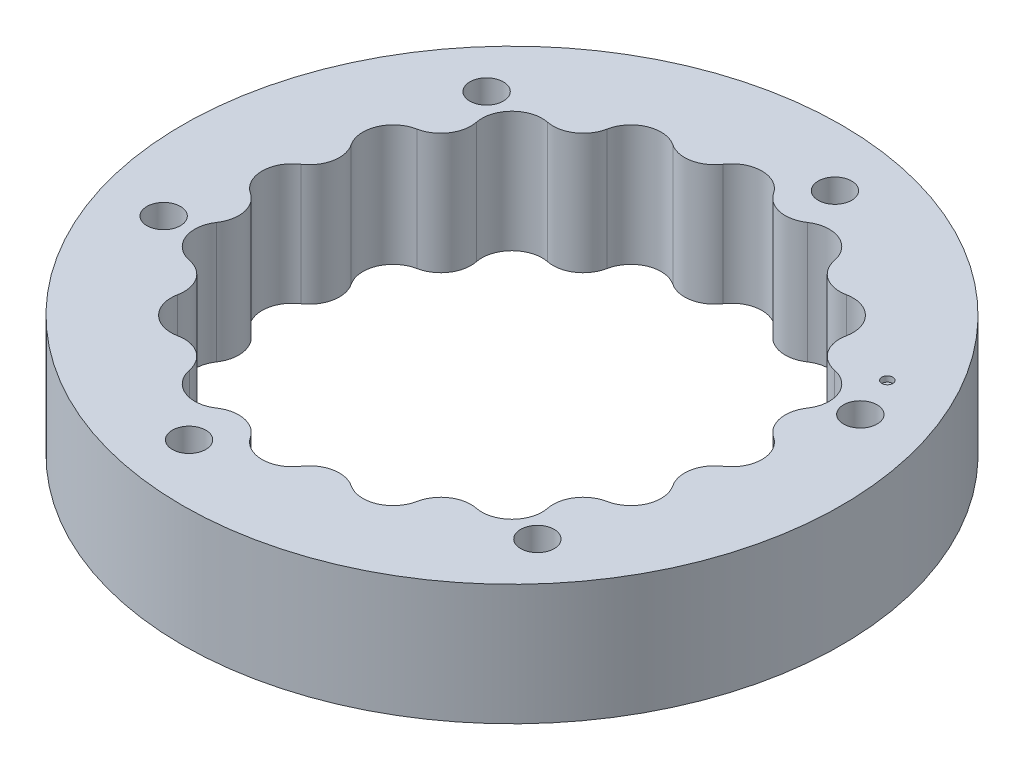
SolidWorks part; units mm, degrees
ref_plane "Front Plane" through (0, 0, 0) normal (0, 0, 1) x (1, 0, 0)
ref_plane "Top Plane" through (0, 0, 0) normal (0, 1, 0) x (1, 0, 0)
ref_plane "Right Plane" through (0, 0, 0) normal (1, 0, 0) x (0, 0, -1)
sketch "Sketch1" plane through (0, 0, 0) normal (0, 1, 0) x (1, 0, 0)
  arc A0 (-31.5919, 24.5347) -> (-34.7568, 19.7981) centre (0, 0) ccw
  arc A1 (4.9902, 39.6875) -> (-4.9902, 39.6875) centre (0, 40) ccw
  arc A2 (19.7981, 34.7568) -> (10.5774, 38.5761) centre (15.3073, 36.9552) ccw
  arc A3 (-31.5919, 24.5347) -> (-34.7568, 19.7981) centre (0, 0) ccw construction
  arc A4 (31.5919, 24.5347) -> (24.5347, 31.5919) centre (28.2843, 28.2843) ccw
  arc A5 (-31.5919, 24.5347) -> (-34.7568, 19.7981) centre (0, 0) ccw construction
  arc A6 (38.5761, 10.5774) -> (34.7568, 19.7981) centre (36.9552, 15.3073) ccw
  arc A7 (-31.5919, 24.5347) -> (-34.7568, 19.7981) centre (0, 0) ccw construction
  arc A8 (39.6875, -4.9902) -> (39.6875, 4.9902) centre (40, 0) ccw
  arc A9 (-31.5919, 24.5347) -> (-34.7568, 19.7981) centre (0, 0) ccw construction
  arc A10 (34.7568, -19.7981) -> (38.5761, -10.5774) centre (36.9552, -15.3073) ccw
  arc A11 (-31.5919, 24.5347) -> (-34.7568, 19.7981) centre (0, 0) ccw construction
  arc A12 (24.5347, -31.5919) -> (31.5919, -24.5347) centre (28.2843, -28.2843) ccw
  arc A13 (-31.5919, 24.5347) -> (-34.7568, 19.7981) centre (0, 0) ccw construction
  arc A14 (10.5774, -38.5761) -> (19.7981, -34.7568) centre (15.3073, -36.9552) ccw
  arc A15 (-31.5919, 24.5347) -> (-34.7568, 19.7981) centre (0, 0) ccw construction
  arc A16 (-4.9902, -39.6875) -> (4.9902, -39.6875) centre (0, -40) ccw
  arc A17 (-31.5919, 24.5347) -> (-34.7568, 19.7981) centre (0, 0) ccw construction
  arc A18 (-19.7981, -34.7568) -> (-10.5774, -38.5761) centre (-15.3073, -36.9552) ccw
  arc A19 (-31.5919, 24.5347) -> (-34.7568, 19.7981) centre (0, 0) ccw construction
  arc A20 (-31.5919, -24.5347) -> (-24.5347, -31.5919) centre (-28.2843, -28.2843) ccw
  arc A21 (-31.5919, 24.5347) -> (-34.7568, 19.7981) centre (0, 0) ccw construction
  arc A22 (-38.5761, -10.5774) -> (-34.7568, -19.7981) centre (-36.9552, -15.3073) ccw
  arc A23 (-31.5919, 24.5347) -> (-34.7568, 19.7981) centre (0, 0) ccw construction
  arc A24 (-39.6875, 4.9902) -> (-39.6875, -4.9902) centre (-40, 0) ccw
  arc A25 (-31.5919, 24.5347) -> (-34.7568, 19.7981) centre (0, 0) ccw construction
  arc A26 (-34.7568, 19.7981) -> (-38.5761, 10.5774) centre (-36.9552, 15.3073) ccw
  arc A27 (-31.5919, 24.5347) -> (-34.7568, 19.7981) centre (0, 0) ccw construction
  arc A28 (-24.5347, 31.5919) -> (-31.5919, 24.5347) centre (-28.2843, 28.2843) ccw
  arc A29 (-31.5919, 24.5347) -> (-34.7568, 19.7981) centre (0, 0) ccw construction
  arc A30 (-10.5774, 38.5761) -> (-19.7981, 34.7568) centre (-15.3073, 36.9552) ccw
  arc A31 (-31.5919, 24.5347) -> (-34.7568, 19.7981) centre (0, 0) ccw construction
  circle A32 centre (0, 0) radius 60
  arc A33 (-19.7981, 34.7568) -> (-24.5347, 31.5919) centre (0, 0) ccw
  arc A34 (-19.7981, 34.7568) -> (-24.5347, 31.5919) centre (0, 0) ccw construction
  arc A35 (-19.7981, 34.7568) -> (-24.5347, 31.5919) centre (0, 0) ccw construction
  arc A36 (-19.7981, 34.7568) -> (-24.5347, 31.5919) centre (0, 0) ccw construction
  arc A37 (-19.7981, 34.7568) -> (-24.5347, 31.5919) centre (0, 0) ccw construction
  arc A38 (-19.7981, 34.7568) -> (-24.5347, 31.5919) centre (0, 0) ccw construction
  arc A39 (-19.7981, 34.7568) -> (-24.5347, 31.5919) centre (0, 0) ccw construction
  arc A40 (-19.7981, 34.7568) -> (-24.5347, 31.5919) centre (0, 0) ccw construction
  arc A41 (-19.7981, 34.7568) -> (-24.5347, 31.5919) centre (0, 0) ccw construction
  arc A42 (-19.7981, 34.7568) -> (-24.5347, 31.5919) centre (0, 0) ccw construction
  arc A43 (-19.7981, 34.7568) -> (-24.5347, 31.5919) centre (0, 0) ccw construction
  arc A44 (-19.7981, 34.7568) -> (-24.5347, 31.5919) centre (0, 0) ccw construction
  arc A45 (-19.7981, 34.7568) -> (-24.5347, 31.5919) centre (0, 0) ccw construction
  arc A46 (-19.7981, 34.7568) -> (-24.5347, 31.5919) centre (0, 0) ccw construction
  arc A47 (-19.7981, 34.7568) -> (-24.5347, 31.5919) centre (0, 0) ccw construction
  arc A48 (-19.7981, 34.7568) -> (-24.5347, 31.5919) centre (0, 0) ccw construction
  arc A49 (-4.9902, 39.6875) -> (-10.5774, 38.5761) centre (0, 0) ccw
  arc A50 (-4.9902, 39.6875) -> (-10.5774, 38.5761) centre (0, 0) ccw construction
  arc A51 (-4.9902, 39.6875) -> (-10.5774, 38.5761) centre (0, 0) ccw construction
  arc A52 (-4.9902, 39.6875) -> (-10.5774, 38.5761) centre (0, 0) ccw construction
  arc A53 (-4.9902, 39.6875) -> (-10.5774, 38.5761) centre (0, 0) ccw construction
  arc A54 (-4.9902, 39.6875) -> (-10.5774, 38.5761) centre (0, 0) ccw construction
  arc A55 (-4.9902, 39.6875) -> (-10.5774, 38.5761) centre (0, 0) ccw construction
  arc A56 (-4.9902, 39.6875) -> (-10.5774, 38.5761) centre (0, 0) ccw construction
  arc A57 (-4.9902, 39.6875) -> (-10.5774, 38.5761) centre (0, 0) ccw construction
  arc A58 (-4.9902, 39.6875) -> (-10.5774, 38.5761) centre (0, 0) ccw construction
  arc A59 (-4.9902, 39.6875) -> (-10.5774, 38.5761) centre (0, 0) ccw construction
  arc A60 (-4.9902, 39.6875) -> (-10.5774, 38.5761) centre (0, 0) ccw construction
  arc A61 (-4.9902, 39.6875) -> (-10.5774, 38.5761) centre (0, 0) ccw construction
  arc A62 (-4.9902, 39.6875) -> (-10.5774, 38.5761) centre (0, 0) ccw construction
  arc A63 (-4.9902, 39.6875) -> (-10.5774, 38.5761) centre (0, 0) ccw construction
  arc A64 (-4.9902, 39.6875) -> (-10.5774, 38.5761) centre (0, 0) ccw construction
  arc A65 (10.5774, 38.5761) -> (4.9902, 39.6875) centre (0, 0) ccw
  arc A66 (10.5774, 38.5761) -> (4.9902, 39.6875) centre (0, 0) ccw construction
  arc A67 (10.5774, 38.5761) -> (4.9902, 39.6875) centre (0, 0) ccw construction
  arc A68 (10.5774, 38.5761) -> (4.9902, 39.6875) centre (0, 0) ccw construction
  arc A69 (10.5774, 38.5761) -> (4.9902, 39.6875) centre (0, 0) ccw construction
  arc A70 (10.5774, 38.5761) -> (4.9902, 39.6875) centre (0, 0) ccw construction
  arc A71 (10.5774, 38.5761) -> (4.9902, 39.6875) centre (0, 0) ccw construction
  arc A72 (10.5774, 38.5761) -> (4.9902, 39.6875) centre (0, 0) ccw construction
  arc A73 (10.5774, 38.5761) -> (4.9902, 39.6875) centre (0, 0) ccw construction
  arc A74 (10.5774, 38.5761) -> (4.9902, 39.6875) centre (0, 0) ccw construction
  arc A75 (10.5774, 38.5761) -> (4.9902, 39.6875) centre (0, 0) ccw construction
  arc A76 (10.5774, 38.5761) -> (4.9902, 39.6875) centre (0, 0) ccw construction
  arc A77 (10.5774, 38.5761) -> (4.9902, 39.6875) centre (0, 0) ccw construction
  arc A78 (10.5774, 38.5761) -> (4.9902, 39.6875) centre (0, 0) ccw construction
  arc A79 (10.5774, 38.5761) -> (4.9902, 39.6875) centre (0, 0) ccw construction
  arc A80 (10.5774, 38.5761) -> (4.9902, 39.6875) centre (0, 0) ccw construction
  arc A81 (24.5347, 31.5919) -> (19.7981, 34.7568) centre (0, 0) ccw
  arc A82 (24.5347, 31.5919) -> (19.7981, 34.7568) centre (0, 0) ccw construction
  arc A83 (24.5347, 31.5919) -> (19.7981, 34.7568) centre (0, 0) ccw construction
  arc A84 (24.5347, 31.5919) -> (19.7981, 34.7568) centre (0, 0) ccw construction
  arc A85 (24.5347, 31.5919) -> (19.7981, 34.7568) centre (0, 0) ccw construction
  arc A86 (24.5347, 31.5919) -> (19.7981, 34.7568) centre (0, 0) ccw construction
  arc A87 (24.5347, 31.5919) -> (19.7981, 34.7568) centre (0, 0) ccw construction
  arc A88 (24.5347, 31.5919) -> (19.7981, 34.7568) centre (0, 0) ccw construction
  arc A89 (24.5347, 31.5919) -> (19.7981, 34.7568) centre (0, 0) ccw construction
  arc A90 (24.5347, 31.5919) -> (19.7981, 34.7568) centre (0, 0) ccw construction
  arc A91 (24.5347, 31.5919) -> (19.7981, 34.7568) centre (0, 0) ccw construction
  arc A92 (24.5347, 31.5919) -> (19.7981, 34.7568) centre (0, 0) ccw construction
  arc A93 (24.5347, 31.5919) -> (19.7981, 34.7568) centre (0, 0) ccw construction
  arc A94 (24.5347, 31.5919) -> (19.7981, 34.7568) centre (0, 0) ccw construction
  arc A95 (24.5347, 31.5919) -> (19.7981, 34.7568) centre (0, 0) ccw construction
  arc A96 (24.5347, 31.5919) -> (19.7981, 34.7568) centre (0, 0) ccw construction
  arc A97 (34.7568, 19.7981) -> (31.5919, 24.5347) centre (0, 0) ccw
  arc A98 (34.7568, 19.7981) -> (31.5919, 24.5347) centre (0, 0) ccw construction
  arc A99 (34.7568, 19.7981) -> (31.5919, 24.5347) centre (0, 0) ccw construction
  arc A100 (34.7568, 19.7981) -> (31.5919, 24.5347) centre (0, 0) ccw construction
  arc A101 (34.7568, 19.7981) -> (31.5919, 24.5347) centre (0, 0) ccw construction
  arc A102 (34.7568, 19.7981) -> (31.5919, 24.5347) centre (0, 0) ccw construction
  arc A103 (34.7568, 19.7981) -> (31.5919, 24.5347) centre (0, 0) ccw construction
  arc A104 (34.7568, 19.7981) -> (31.5919, 24.5347) centre (0, 0) ccw construction
  arc A105 (34.7568, 19.7981) -> (31.5919, 24.5347) centre (0, 0) ccw construction
  arc A106 (34.7568, 19.7981) -> (31.5919, 24.5347) centre (0, 0) ccw construction
  arc A107 (34.7568, 19.7981) -> (31.5919, 24.5347) centre (0, 0) ccw construction
  arc A108 (34.7568, 19.7981) -> (31.5919, 24.5347) centre (0, 0) ccw construction
  arc A109 (34.7568, 19.7981) -> (31.5919, 24.5347) centre (0, 0) ccw construction
  arc A110 (34.7568, 19.7981) -> (31.5919, 24.5347) centre (0, 0) ccw construction
  arc A111 (34.7568, 19.7981) -> (31.5919, 24.5347) centre (0, 0) ccw construction
  arc A112 (34.7568, 19.7981) -> (31.5919, 24.5347) centre (0, 0) ccw construction
  arc A113 (39.6875, 4.9902) -> (38.5761, 10.5774) centre (0, 0) ccw
  arc A114 (39.6875, 4.9902) -> (38.5761, 10.5774) centre (0, 0) ccw construction
  arc A115 (39.6875, 4.9902) -> (38.5761, 10.5774) centre (0, 0) ccw construction
  arc A116 (39.6875, 4.9902) -> (38.5761, 10.5774) centre (0, 0) ccw construction
  arc A117 (39.6875, 4.9902) -> (38.5761, 10.5774) centre (0, 0) ccw construction
  arc A118 (39.6875, 4.9902) -> (38.5761, 10.5774) centre (0, 0) ccw construction
  arc A119 (39.6875, 4.9902) -> (38.5761, 10.5774) centre (0, 0) ccw construction
  arc A120 (39.6875, 4.9902) -> (38.5761, 10.5774) centre (0, 0) ccw construction
  arc A121 (39.6875, 4.9902) -> (38.5761, 10.5774) centre (0, 0) ccw construction
  arc A122 (39.6875, 4.9902) -> (38.5761, 10.5774) centre (0, 0) ccw construction
  arc A123 (39.6875, 4.9902) -> (38.5761, 10.5774) centre (0, 0) ccw construction
  arc A124 (39.6875, 4.9902) -> (38.5761, 10.5774) centre (0, 0) ccw construction
  arc A125 (39.6875, 4.9902) -> (38.5761, 10.5774) centre (0, 0) ccw construction
  arc A126 (39.6875, 4.9902) -> (38.5761, 10.5774) centre (0, 0) ccw construction
  arc A127 (39.6875, 4.9902) -> (38.5761, 10.5774) centre (0, 0) ccw construction
  arc A128 (39.6875, 4.9902) -> (38.5761, 10.5774) centre (0, 0) ccw construction
  arc A129 (38.5761, -10.5774) -> (39.6875, -4.9902) centre (0, 0) ccw
  arc A130 (38.5761, -10.5774) -> (39.6875, -4.9902) centre (0, 0) ccw construction
  arc A131 (38.5761, -10.5774) -> (39.6875, -4.9902) centre (0, 0) ccw construction
  arc A132 (38.5761, -10.5774) -> (39.6875, -4.9902) centre (0, 0) ccw construction
  arc A133 (38.5761, -10.5774) -> (39.6875, -4.9902) centre (0, 0) ccw construction
  arc A134 (38.5761, -10.5774) -> (39.6875, -4.9902) centre (0, 0) ccw construction
  arc A135 (38.5761, -10.5774) -> (39.6875, -4.9902) centre (0, 0) ccw construction
  arc A136 (38.5761, -10.5774) -> (39.6875, -4.9902) centre (0, 0) ccw construction
  arc A137 (38.5761, -10.5774) -> (39.6875, -4.9902) centre (0, 0) ccw construction
  arc A138 (38.5761, -10.5774) -> (39.6875, -4.9902) centre (0, 0) ccw construction
  arc A139 (38.5761, -10.5774) -> (39.6875, -4.9902) centre (0, 0) ccw construction
  arc A140 (38.5761, -10.5774) -> (39.6875, -4.9902) centre (0, 0) ccw construction
  arc A141 (38.5761, -10.5774) -> (39.6875, -4.9902) centre (0, 0) ccw construction
  arc A142 (38.5761, -10.5774) -> (39.6875, -4.9902) centre (0, 0) ccw construction
  arc A143 (38.5761, -10.5774) -> (39.6875, -4.9902) centre (0, 0) ccw construction
  arc A144 (38.5761, -10.5774) -> (39.6875, -4.9902) centre (0, 0) ccw construction
  arc A145 (31.5919, -24.5347) -> (34.7568, -19.7981) centre (0, 0) ccw
  arc A146 (31.5919, -24.5347) -> (34.7568, -19.7981) centre (0, 0) ccw construction
  arc A147 (31.5919, -24.5347) -> (34.7568, -19.7981) centre (0, 0) ccw construction
  arc A148 (31.5919, -24.5347) -> (34.7568, -19.7981) centre (0, 0) ccw construction
  arc A149 (31.5919, -24.5347) -> (34.7568, -19.7981) centre (0, 0) ccw construction
  arc A150 (31.5919, -24.5347) -> (34.7568, -19.7981) centre (0, 0) ccw construction
  arc A151 (31.5919, -24.5347) -> (34.7568, -19.7981) centre (0, 0) ccw construction
  arc A152 (31.5919, -24.5347) -> (34.7568, -19.7981) centre (0, 0) ccw construction
  arc A153 (31.5919, -24.5347) -> (34.7568, -19.7981) centre (0, 0) ccw construction
  arc A154 (31.5919, -24.5347) -> (34.7568, -19.7981) centre (0, 0) ccw construction
  arc A155 (31.5919, -24.5347) -> (34.7568, -19.7981) centre (0, 0) ccw construction
  arc A156 (31.5919, -24.5347) -> (34.7568, -19.7981) centre (0, 0) ccw construction
  arc A157 (31.5919, -24.5347) -> (34.7568, -19.7981) centre (0, 0) ccw construction
  arc A158 (31.5919, -24.5347) -> (34.7568, -19.7981) centre (0, 0) ccw construction
  arc A159 (31.5919, -24.5347) -> (34.7568, -19.7981) centre (0, 0) ccw construction
  arc A160 (31.5919, -24.5347) -> (34.7568, -19.7981) centre (0, 0) ccw construction
  arc A161 (19.7981, -34.7568) -> (24.5347, -31.5919) centre (0, 0) ccw
  arc A162 (19.7981, -34.7568) -> (24.5347, -31.5919) centre (0, 0) ccw construction
  arc A163 (19.7981, -34.7568) -> (24.5347, -31.5919) centre (0, 0) ccw construction
  arc A164 (19.7981, -34.7568) -> (24.5347, -31.5919) centre (0, 0) ccw construction
  arc A165 (19.7981, -34.7568) -> (24.5347, -31.5919) centre (0, 0) ccw construction
  arc A166 (19.7981, -34.7568) -> (24.5347, -31.5919) centre (0, 0) ccw construction
  arc A167 (19.7981, -34.7568) -> (24.5347, -31.5919) centre (0, 0) ccw construction
  arc A168 (19.7981, -34.7568) -> (24.5347, -31.5919) centre (0, 0) ccw construction
  arc A169 (19.7981, -34.7568) -> (24.5347, -31.5919) centre (0, 0) ccw construction
  arc A170 (19.7981, -34.7568) -> (24.5347, -31.5919) centre (0, 0) ccw construction
  arc A171 (19.7981, -34.7568) -> (24.5347, -31.5919) centre (0, 0) ccw construction
  arc A172 (19.7981, -34.7568) -> (24.5347, -31.5919) centre (0, 0) ccw construction
  arc A173 (19.7981, -34.7568) -> (24.5347, -31.5919) centre (0, 0) ccw construction
  arc A174 (19.7981, -34.7568) -> (24.5347, -31.5919) centre (0, 0) ccw construction
  arc A175 (19.7981, -34.7568) -> (24.5347, -31.5919) centre (0, 0) ccw construction
  arc A176 (19.7981, -34.7568) -> (24.5347, -31.5919) centre (0, 0) ccw construction
  arc A177 (4.9902, -39.6875) -> (10.5774, -38.5761) centre (0, 0) ccw
  arc A178 (4.9902, -39.6875) -> (10.5774, -38.5761) centre (0, 0) ccw construction
  arc A179 (4.9902, -39.6875) -> (10.5774, -38.5761) centre (0, 0) ccw construction
  arc A180 (4.9902, -39.6875) -> (10.5774, -38.5761) centre (0, 0) ccw construction
  arc A181 (4.9902, -39.6875) -> (10.5774, -38.5761) centre (0, 0) ccw construction
  arc A182 (4.9902, -39.6875) -> (10.5774, -38.5761) centre (0, 0) ccw construction
  arc A183 (4.9902, -39.6875) -> (10.5774, -38.5761) centre (0, 0) ccw construction
  arc A184 (4.9902, -39.6875) -> (10.5774, -38.5761) centre (0, 0) ccw construction
  arc A185 (4.9902, -39.6875) -> (10.5774, -38.5761) centre (0, 0) ccw construction
  arc A186 (4.9902, -39.6875) -> (10.5774, -38.5761) centre (0, 0) ccw construction
  arc A187 (4.9902, -39.6875) -> (10.5774, -38.5761) centre (0, 0) ccw construction
  arc A188 (4.9902, -39.6875) -> (10.5774, -38.5761) centre (0, 0) ccw construction
  arc A189 (4.9902, -39.6875) -> (10.5774, -38.5761) centre (0, 0) ccw construction
  arc A190 (4.9902, -39.6875) -> (10.5774, -38.5761) centre (0, 0) ccw construction
  arc A191 (4.9902, -39.6875) -> (10.5774, -38.5761) centre (0, 0) ccw construction
  arc A192 (4.9902, -39.6875) -> (10.5774, -38.5761) centre (0, 0) ccw construction
  arc A193 (-10.5774, -38.5761) -> (-4.9902, -39.6875) centre (0, 0) ccw
  arc A194 (-10.5774, -38.5761) -> (-4.9902, -39.6875) centre (0, 0) ccw construction
  arc A195 (-10.5774, -38.5761) -> (-4.9902, -39.6875) centre (0, 0) ccw construction
  arc A196 (-10.5774, -38.5761) -> (-4.9902, -39.6875) centre (0, 0) ccw construction
  arc A197 (-10.5774, -38.5761) -> (-4.9902, -39.6875) centre (0, 0) ccw construction
  arc A198 (-10.5774, -38.5761) -> (-4.9902, -39.6875) centre (0, 0) ccw construction
  arc A199 (-10.5774, -38.5761) -> (-4.9902, -39.6875) centre (0, 0) ccw construction
  arc A200 (-10.5774, -38.5761) -> (-4.9902, -39.6875) centre (0, 0) ccw construction
  arc A201 (-10.5774, -38.5761) -> (-4.9902, -39.6875) centre (0, 0) ccw construction
  arc A202 (-10.5774, -38.5761) -> (-4.9902, -39.6875) centre (0, 0) ccw construction
  arc A203 (-10.5774, -38.5761) -> (-4.9902, -39.6875) centre (0, 0) ccw construction
  arc A204 (-10.5774, -38.5761) -> (-4.9902, -39.6875) centre (0, 0) ccw construction
  arc A205 (-10.5774, -38.5761) -> (-4.9902, -39.6875) centre (0, 0) ccw construction
  arc A206 (-10.5774, -38.5761) -> (-4.9902, -39.6875) centre (0, 0) ccw construction
  arc A207 (-10.5774, -38.5761) -> (-4.9902, -39.6875) centre (0, 0) ccw construction
  arc A208 (-10.5774, -38.5761) -> (-4.9902, -39.6875) centre (0, 0) ccw construction
  arc A209 (-24.5347, -31.5919) -> (-19.7981, -34.7568) centre (0, 0) ccw
  arc A210 (-24.5347, -31.5919) -> (-19.7981, -34.7568) centre (0, 0) ccw construction
  arc A211 (-24.5347, -31.5919) -> (-19.7981, -34.7568) centre (0, 0) ccw construction
  arc A212 (-24.5347, -31.5919) -> (-19.7981, -34.7568) centre (0, 0) ccw construction
  arc A213 (-24.5347, -31.5919) -> (-19.7981, -34.7568) centre (0, 0) ccw construction
  arc A214 (-24.5347, -31.5919) -> (-19.7981, -34.7568) centre (0, 0) ccw construction
  arc A215 (-24.5347, -31.5919) -> (-19.7981, -34.7568) centre (0, 0) ccw construction
  arc A216 (-24.5347, -31.5919) -> (-19.7981, -34.7568) centre (0, 0) ccw construction
  arc A217 (-24.5347, -31.5919) -> (-19.7981, -34.7568) centre (0, 0) ccw construction
  arc A218 (-24.5347, -31.5919) -> (-19.7981, -34.7568) centre (0, 0) ccw construction
  arc A219 (-24.5347, -31.5919) -> (-19.7981, -34.7568) centre (0, 0) ccw construction
  arc A220 (-24.5347, -31.5919) -> (-19.7981, -34.7568) centre (0, 0) ccw construction
  arc A221 (-24.5347, -31.5919) -> (-19.7981, -34.7568) centre (0, 0) ccw construction
  arc A222 (-24.5347, -31.5919) -> (-19.7981, -34.7568) centre (0, 0) ccw construction
  arc A223 (-24.5347, -31.5919) -> (-19.7981, -34.7568) centre (0, 0) ccw construction
  arc A224 (-24.5347, -31.5919) -> (-19.7981, -34.7568) centre (0, 0) ccw construction
  arc A225 (-34.7568, -19.7981) -> (-31.5919, -24.5347) centre (0, 0) ccw
  arc A226 (-34.7568, -19.7981) -> (-31.5919, -24.5347) centre (0, 0) ccw construction
  arc A227 (-34.7568, -19.7981) -> (-31.5919, -24.5347) centre (0, 0) ccw construction
  arc A228 (-34.7568, -19.7981) -> (-31.5919, -24.5347) centre (0, 0) ccw construction
  arc A229 (-34.7568, -19.7981) -> (-31.5919, -24.5347) centre (0, 0) ccw construction
  arc A230 (-34.7568, -19.7981) -> (-31.5919, -24.5347) centre (0, 0) ccw construction
  arc A231 (-34.7568, -19.7981) -> (-31.5919, -24.5347) centre (0, 0) ccw construction
  arc A232 (-34.7568, -19.7981) -> (-31.5919, -24.5347) centre (0, 0) ccw construction
  arc A233 (-34.7568, -19.7981) -> (-31.5919, -24.5347) centre (0, 0) ccw construction
  arc A234 (-34.7568, -19.7981) -> (-31.5919, -24.5347) centre (0, 0) ccw construction
  arc A235 (-34.7568, -19.7981) -> (-31.5919, -24.5347) centre (0, 0) ccw construction
  arc A236 (-34.7568, -19.7981) -> (-31.5919, -24.5347) centre (0, 0) ccw construction
  arc A237 (-34.7568, -19.7981) -> (-31.5919, -24.5347) centre (0, 0) ccw construction
  arc A238 (-34.7568, -19.7981) -> (-31.5919, -24.5347) centre (0, 0) ccw construction
  arc A239 (-34.7568, -19.7981) -> (-31.5919, -24.5347) centre (0, 0) ccw construction
  arc A240 (-34.7568, -19.7981) -> (-31.5919, -24.5347) centre (0, 0) ccw construction
  arc A241 (-39.6875, -4.9902) -> (-38.5761, -10.5774) centre (0, 0) ccw
  arc A242 (-39.6875, -4.9902) -> (-38.5761, -10.5774) centre (0, 0) ccw construction
  arc A243 (-39.6875, -4.9902) -> (-38.5761, -10.5774) centre (0, 0) ccw construction
  arc A244 (-39.6875, -4.9902) -> (-38.5761, -10.5774) centre (0, 0) ccw construction
  arc A245 (-39.6875, -4.9902) -> (-38.5761, -10.5774) centre (0, 0) ccw construction
  arc A246 (-39.6875, -4.9902) -> (-38.5761, -10.5774) centre (0, 0) ccw construction
  arc A247 (-39.6875, -4.9902) -> (-38.5761, -10.5774) centre (0, 0) ccw construction
  arc A248 (-39.6875, -4.9902) -> (-38.5761, -10.5774) centre (0, 0) ccw construction
  arc A249 (-39.6875, -4.9902) -> (-38.5761, -10.5774) centre (0, 0) ccw construction
  arc A250 (-39.6875, -4.9902) -> (-38.5761, -10.5774) centre (0, 0) ccw construction
  arc A251 (-39.6875, -4.9902) -> (-38.5761, -10.5774) centre (0, 0) ccw construction
  arc A252 (-39.6875, -4.9902) -> (-38.5761, -10.5774) centre (0, 0) ccw construction
  arc A253 (-39.6875, -4.9902) -> (-38.5761, -10.5774) centre (0, 0) ccw construction
  arc A254 (-39.6875, -4.9902) -> (-38.5761, -10.5774) centre (0, 0) ccw construction
  arc A255 (-39.6875, -4.9902) -> (-38.5761, -10.5774) centre (0, 0) ccw construction
  arc A256 (-39.6875, -4.9902) -> (-38.5761, -10.5774) centre (0, 0) ccw construction
  arc A257 (-38.5761, 10.5774) -> (-39.6875, 4.9902) centre (0, 0) ccw
  arc A258 (-38.5761, 10.5774) -> (-39.6875, 4.9902) centre (0, 0) ccw construction
  arc A259 (-38.5761, 10.5774) -> (-39.6875, 4.9902) centre (0, 0) ccw construction
  arc A260 (-38.5761, 10.5774) -> (-39.6875, 4.9902) centre (0, 0) ccw construction
  arc A261 (-38.5761, 10.5774) -> (-39.6875, 4.9902) centre (0, 0) ccw construction
  arc A262 (-38.5761, 10.5774) -> (-39.6875, 4.9902) centre (0, 0) ccw construction
  arc A263 (-38.5761, 10.5774) -> (-39.6875, 4.9902) centre (0, 0) ccw construction
  arc A264 (-38.5761, 10.5774) -> (-39.6875, 4.9902) centre (0, 0) ccw construction
  arc A265 (-38.5761, 10.5774) -> (-39.6875, 4.9902) centre (0, 0) ccw construction
  arc A266 (-38.5761, 10.5774) -> (-39.6875, 4.9902) centre (0, 0) ccw construction
  arc A267 (-38.5761, 10.5774) -> (-39.6875, 4.9902) centre (0, 0) ccw construction
  arc A268 (-38.5761, 10.5774) -> (-39.6875, 4.9902) centre (0, 0) ccw construction
  arc A269 (-38.5761, 10.5774) -> (-39.6875, 4.9902) centre (0, 0) ccw construction
  arc A270 (-38.5761, 10.5774) -> (-39.6875, 4.9902) centre (0, 0) ccw construction
  arc A271 (-38.5761, 10.5774) -> (-39.6875, 4.9902) centre (0, 0) ccw construction
  arc A272 (-38.5761, 10.5774) -> (-39.6875, 4.9902) centre (0, 0) ccw construction
  point P52 (0, 0)
  dimension "D1" = 80
  dimension "D2" = 10
  dimension "D4" = 120
  dimension "D3" = 16
extrude "Boss-Extrude1" add sketch "Sketch1" along normal blind 22
fillet "Fillet1" radius 5 32 edges at (-31.5919, 11, -24.5347) (-34.7568, 11, -19.7981) (10.5774, 11, 38.5761) (4.9902, 11, 39.6875) (-4.9902, 11, 39.6875) (-10.5774, 11, 38.5761) (-19.7981, 11, 34.7568) (-24.5347, 11, 31.5919) (-31.5919, 11, 24.5347) (-34.7568, 11, 19.7981) (-38.5761, 11, 10.5774) (-39.6875, 11, 4.9902) (-39.6875, 11, -4.9902) (-38.5761, 11, -10.5774) (19.7981, 11, 34.7568) (24.5347, 11, 31.5919) (31.5919, 11, 24.5347) (34.7568, 11, 19.7981) (38.5761, 11, 10.5774) (39.6875, 11, 4.9902) (39.6875, 11, -4.9902) (38.5761, 11, -10.5774) (34.7568, 11, -19.7981) (31.5919, 11, -24.5347) (24.5347, 11, -31.5919) (19.7981, 11, -34.7568) (10.5774, 11, -38.5761) (4.9902, 11, -39.6875) (-4.9902, 11, -39.6875) (-10.5774, 11, -38.5761) (-19.7981, 11, -34.7568) (-24.5347, 11, -31.5919)
fillet "Fillet2" radius 6 16 edges at (-7.8059, 11, 39.2431) (7.8059, 11, 39.2431) (22.2294, 11, 33.2687) (33.2687, 11, 22.2294) (-22.2294, 11, 33.2687) (-33.2687, 11, 22.2294) (-39.2431, 11, 7.8059) (-39.2431, 11, -7.8059) (39.2431, 11, 7.8059) (39.2431, 11, -7.8059) (33.2687, 11, -22.2294) (22.2294, 11, -33.2687) (7.8059, 11, -39.2431) (-7.8059, 11, -39.2431) (-22.2294, 11, -33.2687) (-33.2687, 11, -22.2294)
sketch "Sketch3" plane through (0, 22, 0) normal (0, 1, 0) x (1, 0, 0)
  line L0 (7.9956, 40.1966) -> (11.7054, 58.8471) construction
  circle A0 centre (0, 0) radius 50 construction
  circle A4 centre (9.7545, 49.0393) radius 3.05
  arc A5 (4.1664, 42.7642) -> (12.5159, 41.1034) centre (9.1661, 46.0813) ccw construction
  circle A6 centre (0, 0) radius 60 construction
  circle A7 centre (47.3465, 16.072) radius 3.05
  circle A8 centre (37.592, -32.9673) radius 3.05
  circle A9 centre (-9.7545, -49.0393) radius 3.05
  circle A10 centre (-47.3465, -16.072) radius 3.05
  circle A11 centre (-37.592, 32.9673) radius 3.05
  point P13 (9.1661, 46.0813)
  point P31 (0, 0)
  dimension "D1" = 100
  dimension "D2" = 6.1
  dimension "D3" = 6
extrude "Cut-Extrude1" cut sketch "Sketch3" against normal through all
ref_axis "Axis1" [suppressed] through (37.592, 0, 32.9673) along (0, 1, 0)
ref_axis "Axis2" [suppressed] through (-9.7545, 0, 49.0393) along (0, 1, 0)
ref_plane "Plane1" [suppressed] through (13.9187, 0, 41.0033) normal (-0.3214, 0, -0.9469) x (-0.9469, 0, 0.3214)
ref_plane "Plane2" [suppressed] through (19.2864, 0, 56.8158) normal (0.3214, 0, 0.9469) x (0.9469, 0, -0.3214)
ref_plane "Plane3" [suppressed] through (19.6078, 0, 57.7627) normal (0.3214, 0, 0.9469) x (0.9469, 0, -0.3214)
ref_plane "Plane4" [suppressed] through (45.1104, 0, 39.5607) normal (0.7518, 0, 0.6593) x (0, -1, 0)
ref_plane "Plane5" [suppressed] through (45.8622, 0, 40.2201) normal (0.7518, 0, 0.6593) x (0, -1, 0)
sketch "Sketch6" [suppressed] plane through (48.3229, 0, 37.4142) normal (-0.7518, 0, -0.6593) x (-0.6593, 0, 0.7518)
  line L0 (-56.2679, 0) -> (63.7321, 0) construction
  line L1 (-22.8416, 17.6775) -> (-2.6943, 26.1971)
  line L2 (10.1584, 26.1971) -> (30.3057, 17.6775)
  line L3 (-22.8416, 4.3225) -> (-2.6943, -4.1971)
  line L4 (10.1584, -4.1971) -> (30.3057, 4.3225)
  arc A0 (-2.6943, -4.1971) -> (10.1584, -4.1971) centre (3.7321, 11) ccw
  arc A1 (30.3057, 4.3225) -> (30.3057, 17.6775) centre (27.4821, 11) ccw
  arc A2 (-22.8416, 17.6775) -> (-22.8416, 4.3225) centre (-20.0179, 11) ccw
  arc A3 (10.1584, 26.1971) -> (-2.6943, 26.1971) centre (3.7321, 11) ccw
  dimension "D1" = 33
  dimension "D2" = 23.75
  dimension "D3" = 23.75
  dimension "D4" = 11
extrude "Boss-Extrude3" [suppressed] add sketch "Sketch6" against normal up to surface (1.3451 mm away)
sketch "Sketch7" [suppressed] plane through (45.8622, 0, 40.2201) normal (0.7518, 0, 0.6593) x (0.6593, 0, -0.7518)
  circle A0 centre (23.75, 11) radius 3.3
  circle A1 centre (-23.75, 11) radius 3.3
  dimension "D1" = 6.6
extrude "Cut-Extrude3" [suppressed] cut sketch "Sketch7" against normal blind 10.5
chamfer "Chamfer2" [suppressed] distance 1 angle 45
fillet "Fillet3" [suppressed] radius 2
sketch "Sketch8" [suppressed] plane through (45.8622, 0, 40.2201) normal (0.7518, 0, 0.6593) x (0.6593, 0, -0.7518)
  line L1 (-16.3518, 22) -> (16.3518, 22)
  line L2 (-16.3518, 22) -> (-16.3518, 27.5)
  line L3 (-16.3518, 27.5) -> (16.3518, 27.5)
  line L4 (16.3518, 22) -> (16.3518, 27.5)
  line L6 (-16.3518, -5.5) -> (16.3518, -5.5)
  line L7 (-16.3518, -5.5) -> (-16.3518, 0)
  line L8 (-16.3518, 0) -> (16.3518, 0)
  line L9 (16.3518, -5.5) -> (16.3518, 0)
  line L10 (26.5737, 4.3225) -> (6.4263, -4.1971) construction
  line L11 (60, 22) -> (-60, 22) construction
  arc A0 (6.4263, 26.1971) -> (-6.4263, 26.1971) centre (0, 11) ccw construction
  arc A1 (-6.4263, -4.1971) -> (6.4263, -4.1971) centre (0, 11) ccw construction
extrude "Cut-Extrude4" [suppressed] cut sketch "Sketch8" against normal through all
sketch "Sketch9" plane through (0, 22, 0) normal (0, 1, 0) x (1, 0, 0)
  circle A0 centre (44.4252, 23.9053) radius 1
  dimension "D1" = 2
extrude "Cut-Extrude5" cut sketch "Sketch9" against normal blind 1
sketch "Sketch10" [suppressed] plane through (0, 22, 0) normal (0, 1, 0) x (1, 0, 0)
  circle A0 centre (44.4252, 23.9053) radius 1
  dimension "D1" = 2
extrude "Cut-Extrude6" [suppressed] cut sketch "Sketch10" against normal blind 1
sketch "Sketch11" plane through (0, 22, 0) normal (0, 1, 0) x (1, 0, 0)
  arc A69 (-43.0406, 4.5831) -> (-43.0406, -4.5831) centre (-40, 0) ccw
  arc A70 (-43.0406, 4.5831) -> (-41.5182, 12.2367) centre (-46.0813, 9.1661) ccw
  arc A71 (-38.0105, 20.7051) -> (-41.5182, 12.2367) centre (-36.9552, 15.3073) ccw
  arc A72 (-38.0105, 20.7051) -> (-33.675, 27.1936) centre (-39.0658, 26.1029) ccw
  arc A73 (-27.1936, 33.675) -> (-33.675, 27.1936) centre (-28.2843, 28.2843) ccw
  arc A74 (-27.1936, 33.675) -> (-20.7051, 38.0105) centre (-26.1029, 39.0658) ccw
  arc A75 (-12.2367, 41.5182) -> (-20.7051, 38.0105) centre (-15.3073, 36.9552) ccw
  arc A76 (-41.5182, -12.2367) -> (-43.0406, -4.5831) centre (-46.0813, -9.1661) ccw
  arc A77 (-41.5182, -12.2367) -> (-38.0105, -20.7051) centre (-36.9552, -15.3073) ccw
  arc A78 (-33.675, -27.1936) -> (-38.0105, -20.7051) centre (-39.0658, -26.1029) ccw
  arc A79 (-33.675, -27.1936) -> (-27.1936, -33.675) centre (-28.2843, -28.2843) ccw
  arc A80 (-20.7051, -38.0105) -> (-27.1936, -33.675) centre (-26.1029, -39.0658) ccw
  arc A81 (-20.7051, -38.0105) -> (-12.2367, -41.5182) centre (-15.3073, -36.9552) ccw
  arc A82 (-4.5831, -43.0406) -> (-12.2367, -41.5182) centre (-9.1661, -46.0813) ccw
  arc A83 (-4.5831, -43.0406) -> (4.5831, -43.0406) centre (0, -40) ccw
  arc A84 (12.2367, -41.5182) -> (4.5831, -43.0406) centre (9.1661, -46.0813) ccw
  arc A85 (12.2367, -41.5182) -> (20.7051, -38.0105) centre (15.3073, -36.9552) ccw
  arc A86 (27.1936, -33.675) -> (20.7051, -38.0105) centre (26.1029, -39.0658) ccw
  arc A87 (27.1936, -33.675) -> (33.675, -27.1936) centre (28.2843, -28.2843) ccw
  arc A88 (38.0105, -20.7051) -> (33.675, -27.1936) centre (39.0658, -26.1029) ccw
  arc A89 (38.0105, -20.7051) -> (41.5182, -12.2367) centre (36.9552, -15.3073) ccw
  arc A90 (43.0406, -4.5831) -> (41.5182, -12.2367) centre (46.0813, -9.1661) ccw
  arc A91 (43.0406, -4.5831) -> (43.0406, 4.5831) centre (40, 0) ccw
  arc A92 (41.5182, 12.2367) -> (43.0406, 4.5831) centre (46.0813, 9.1661) ccw
  arc A93 (41.5182, 12.2367) -> (38.0105, 20.7051) centre (36.9552, 15.3073) ccw
  arc A94 (33.675, 27.1936) -> (38.0105, 20.7051) centre (39.0658, 26.1029) ccw
  arc A95 (33.675, 27.1936) -> (27.1936, 33.675) centre (28.2843, 28.2843) ccw
  arc A96 (20.7051, 38.0105) -> (27.1936, 33.675) centre (26.1029, 39.0658) ccw
  arc A97 (20.7051, 38.0105) -> (12.2367, 41.5182) centre (15.3073, 36.9552) ccw
  arc A98 (4.5831, 43.0406) -> (12.2367, 41.5182) centre (9.1661, 46.0813) ccw
  arc A99 (4.5831, 43.0406) -> (-4.5831, 43.0406) centre (0, 40) ccw
  arc A100 (-12.2367, 41.5182) -> (-4.5831, 43.0406) centre (-9.1661, 46.0813) ccw
  arc A101 (-43.0406, 4.5831) -> (-43.0406, -4.5831) centre (-40, 0) ccw
  arc A102 (-43.0406, 4.5831) -> (-41.5182, 12.2367) centre (-46.0813, 9.1661) ccw
  arc A103 (-38.0105, 20.7051) -> (-41.5182, 12.2367) centre (-36.9552, 15.3073) ccw
  arc A104 (-38.0105, 20.7051) -> (-33.675, 27.1936) centre (-39.0658, 26.1029) ccw
  arc A105 (-27.1936, 33.675) -> (-33.675, 27.1936) centre (-28.2843, 28.2843) ccw
  arc A106 (-27.1936, 33.675) -> (-20.7051, 38.0105) centre (-26.1029, 39.0658) ccw
  arc A107 (-12.2367, 41.5182) -> (-20.7051, 38.0105) centre (-15.3073, 36.9552) ccw
  arc A108 (-41.5182, -12.2367) -> (-43.0406, -4.5831) centre (-46.0813, -9.1661) ccw
  arc A109 (-41.5182, -12.2367) -> (-38.0105, -20.7051) centre (-36.9552, -15.3073) ccw
  arc A110 (-33.675, -27.1936) -> (-38.0105, -20.7051) centre (-39.0658, -26.1029) ccw
  arc A111 (-33.675, -27.1936) -> (-27.1936, -33.675) centre (-28.2843, -28.2843) ccw
  arc A112 (-20.7051, -38.0105) -> (-27.1936, -33.675) centre (-26.1029, -39.0658) ccw
  arc A113 (-20.7051, -38.0105) -> (-12.2367, -41.5182) centre (-15.3073, -36.9552) ccw
  arc A114 (-4.5831, -43.0406) -> (-12.2367, -41.5182) centre (-9.1661, -46.0813) ccw
  arc A115 (-4.5831, -43.0406) -> (4.5831, -43.0406) centre (0, -40) ccw
  arc A116 (12.2367, -41.5182) -> (4.5831, -43.0406) centre (9.1661, -46.0813) ccw
  arc A117 (12.2367, -41.5182) -> (20.7051, -38.0105) centre (15.3073, -36.9552) ccw
  arc A118 (27.1936, -33.675) -> (20.7051, -38.0105) centre (26.1029, -39.0658) ccw
  arc A119 (27.1936, -33.675) -> (33.675, -27.1936) centre (28.2843, -28.2843) ccw
  arc A120 (38.0105, -20.7051) -> (33.675, -27.1936) centre (39.0658, -26.1029) ccw
  arc A121 (38.0105, -20.7051) -> (41.5182, -12.2367) centre (36.9552, -15.3073) ccw
  arc A122 (43.0406, -4.5831) -> (41.5182, -12.2367) centre (46.0813, -9.1661) ccw
  arc A123 (43.0406, -4.5831) -> (43.0406, 4.5831) centre (40, 0) ccw
  arc A124 (41.5182, 12.2367) -> (43.0406, 4.5831) centre (46.0813, 9.1661) ccw
  arc A125 (41.5182, 12.2367) -> (38.0105, 20.7051) centre (36.9552, 15.3073) ccw
  arc A126 (33.675, 27.1936) -> (38.0105, 20.7051) centre (39.0658, 26.1029) ccw
  arc A127 (33.675, 27.1936) -> (27.1936, 33.675) centre (28.2843, 28.2843) ccw
  arc A128 (20.7051, 38.0105) -> (27.1936, 33.675) centre (26.1029, 39.0658) ccw
  arc A129 (20.7051, 38.0105) -> (12.2367, 41.5182) centre (15.3073, 36.9552) ccw
  arc A130 (4.5831, 43.0406) -> (12.2367, 41.5182) centre (9.1661, 46.0813) ccw
  arc A131 (4.5831, 43.0406) -> (-4.5831, 43.0406) centre (0, 40) ccw
  arc A132 (-12.2367, 41.5182) -> (-4.5831, 43.0406) centre (-9.1661, 46.0813) ccw
  dimension "D1" = 0.5
extrude "Cut-Extrude7" cut sketch "Sketch11" against normal through all
equation "\"R_ROLL\"= 5mm"
equation "\"D_SUN\"= 80mm"
equation "\"NUM_ROLL\"= 16"
equation "\"RHO\"= 1mm"
equation "\"D_SHAFT\"= 15mm"
equation "\"D_OUTPUT\"= 40mm"
equation "\"NUM_OUT\"= 6"
equation "\"R_OUT_ROLL\"= 5mm"
equation "\"D1@Sketch1\"=\"D_SUN\""
equation "\"D2@Sketch1\"=\"R_ROLL\"*2"
equation "\"D3@Sketch1\"=\"NUM_ROLL\""
equation "\"D4@Sketch1\"=\"D_SUN\"+40"
